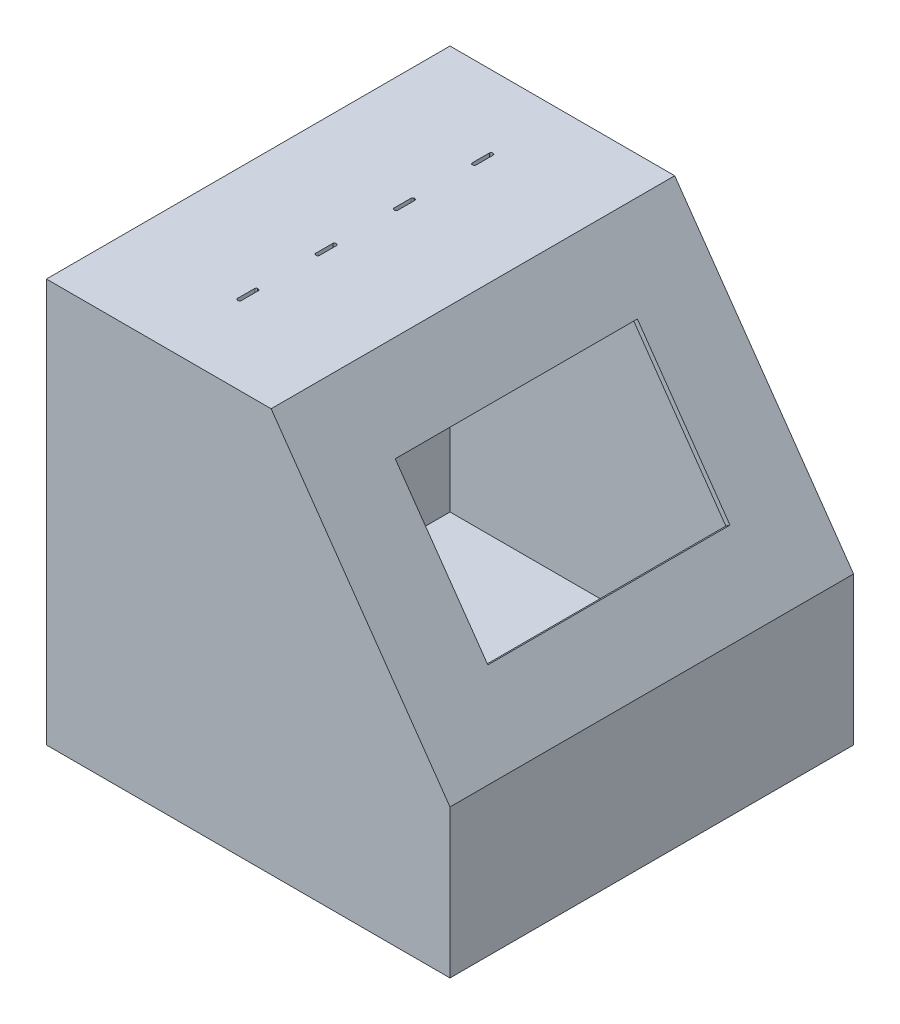
SolidWorks part; units mm, degrees
material "Polyethylene Cross-Linked"
ref_plane "Front Plane" through (0, 0, 0) normal (0, 0, 1) x (1, 0, 0)
ref_plane "Top Plane" through (0, 0, 0) normal (0, 1, 0) x (1, 0, 0)
ref_plane "Right Plane" through (0, 0, 0) normal (1, 0, 0) x (0, 0, -1)
sketch "Sketch1" plane through (0, 0, 0) normal (0, 0, 1) x (1, 0, 0)
  line L0 (0, 101.6) -> (0, 609.6)
  line L3 (0, 101.6) -> (508, 101.6)
  line L5 (0, 609.6) -> (282.847, 609.6)
  line L6 (282.847, 609.6) -> (508, 288.0481)
  line L8 (508, 288.0481) -> (508, 101.6)
  point P5 (0, 0)
  point P7 (513.4774, 269.6483)
  dimension "D2" = 508
  dimension "D4" = 215
  dimension "D5" = 392.5424
extrude "Boss-Extrude1" add sketch "Sketch1" along normal blind 508 contours L8 L6 L5 L0 L3 | L3 L8 L6 L5 L0 region at (224.8029, 331.6457, 0)
sketch "Sketch3" plane through (-2211.0423, 4171.243, 0) normal (-0.8192, -0.5736, 0) x (0, 0, -1)
  line L0 (0, 4347.9633) -> (0, 4740.5056) construction
  line L1 (-406.4, 4646.4133) -> (-101.6, 4646.4133)
  line L2 (-406.4, 4646.4133) -> (-406.4, 4443.2133)
  line L3 (-406.4, 4443.2133) -> (-101.6, 4443.2133)
  line L4 (-101.6, 4646.4133) -> (-101.6, 4443.2133)
  line L5 (-508, 4347.9633) -> (0, 4347.9633) construction
  dimension "D1" = 203.2
  dimension "D2" = 304.8
  dimension "D3" = 101.6
  dimension "D4" = 95.25
extrude "Cut-Extrude3" cut sketch "Sketch3" along normal blind 6.35
shell "Shell2" thickness 6.35 removed face at (390.5539, 444.7077, 254)
sketch "Sketch9" [suppressed] plane through (0, 371.2483, 0) normal (0, 1, 0) x (1, 0, 0)
sketch "Sketch10" plane through (0, 609.6, 0) normal (0, 1, 0) x (1, 0, 0)
  line L16 (143.382, -385.4514) -> (144.182, -385.4514)
  line L17 (141.382, -408.9514) -> (141.382, -387.4514)
  line L18 (146.182, -387.4514) -> (146.182, -408.9514)
  line L19 (144.182, -410.9514) -> (143.382, -410.9514)
  line L20 (144.182, -312.4389) -> (143.382, -312.4389)
  line L21 (146.182, -288.9389) -> (146.182, -310.4389)
  line L22 (141.382, -310.4389) -> (141.382, -288.9389)
  line L23 (143.382, -286.9389) -> (144.182, -286.9389)
  line L24 (144.182, -213.9263) -> (143.382, -213.9263)
  line L25 (141.382, -211.9263) -> (141.382, -190.4263)
  line L26 (146.182, -190.4263) -> (146.182, -211.9263)
  line L27 (143.382, -188.4263) -> (144.182, -188.4263)
  line L28 (144.182, -115.4137) -> (143.382, -115.4137)
  line L29 (141.382, -113.4137) -> (141.382, -91.9137)
  line L30 (143.382, -89.9137) -> (144.182, -89.9137)
  line L31 (146.182, -91.9137) -> (146.182, -113.4137)
  arc A16 (146.182, -387.4514) -> (144.182, -385.4514) centre (144.182, -387.4514) ccw
  arc A17 (143.382, -385.4514) -> (141.382, -387.4514) centre (143.382, -387.4514) ccw
  arc A18 (144.182, -410.9514) -> (146.182, -408.9514) centre (144.182, -408.9514) ccw
  arc A19 (141.382, -408.9514) -> (143.382, -410.9514) centre (143.382, -408.9514) ccw
  arc A20 (144.182, -312.4389) -> (146.182, -310.4389) centre (144.182, -310.4389) ccw
  arc A21 (141.382, -310.4389) -> (143.382, -312.4389) centre (143.382, -310.4389) ccw
  arc A22 (143.382, -286.9389) -> (141.382, -288.9389) centre (143.382, -288.9389) ccw
  arc A23 (146.182, -288.9389) -> (144.182, -286.9389) centre (144.182, -288.9389) ccw
  arc A24 (144.182, -213.9263) -> (146.182, -211.9263) centre (144.182, -211.9263) ccw
  arc A25 (141.382, -211.9263) -> (143.382, -213.9263) centre (143.382, -211.9263) ccw
  arc A26 (146.182, -190.4263) -> (144.182, -188.4263) centre (144.182, -190.4263) ccw
  arc A27 (143.382, -188.4263) -> (141.382, -190.4263) centre (143.382, -190.4263) ccw
  arc A28 (141.382, -113.4137) -> (143.382, -115.4137) centre (143.382, -113.4137) ccw
  arc A29 (144.182, -115.4137) -> (146.182, -113.4137) centre (144.182, -113.4137) ccw
  arc A30 (143.382, -89.9137) -> (141.382, -91.9137) centre (143.382, -91.9137) ccw
  arc A31 (146.182, -91.9137) -> (144.182, -89.9137) centre (144.182, -91.9137) ccw
extrude "Cut-Extrude5" cut sketch "Sketch10" against normal up to next contours A16 L16 A17 L17 A19 L19 A18 L18 | A20 L21 A23 L23 A22 L22 A21 L20 | L24 A25 L25 A27 L27 A26 L26 A24 | A28 L28 A29 L31 A31 L30 A30 L29
ref_plane "Plane1" through (0, 0, 254) normal (0, 0, 1) x (1, 0, 0)
